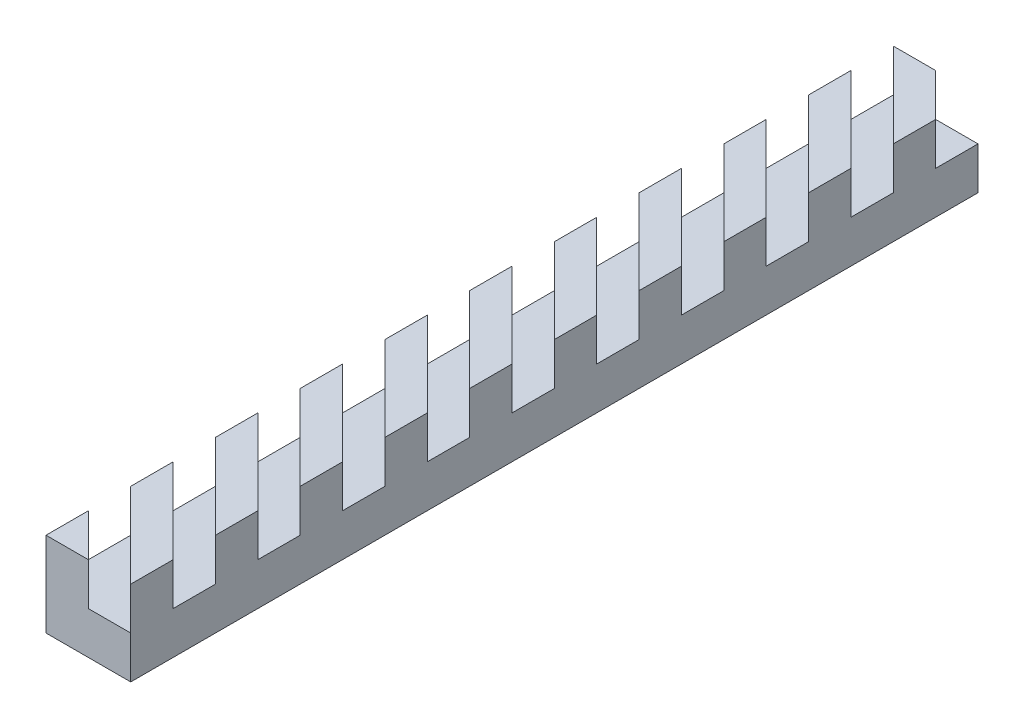
SolidWorks part; units mm, degrees
ref_plane "Front Plane" through (0, 0, 0) normal (0, 0, 1) x (1, 0, 0)
ref_plane "Top Plane" through (0, 0, 0) normal (0, 1, 0) x (1, 0, 0)
ref_plane "Right Plane" through (0, 0, 0) normal (1, 0, 0) x (0, 0, -1)
sketch "Sketch1" plane through (0, 0, 0) normal (0, 0, 1) x (1, 0, 0)
  line L1 (-53.9409, 54.9261) -> (46.0591, 54.9261)
  line L2 (-53.9409, 54.9261) -> (-53.9409, -45.0739)
  line L3 (-53.9409, -45.0739) -> (46.0591, -45.0739)
  line L4 (46.0591, 54.9261) -> (46.0591, -45.0739)
  dimension "D1" = 100
  dimension "D2" = 100
extrude "Boss-Extrude1" add sketch "Sketch1" against normal blind 1000
sketch "Sketch2" plane through (46.0591, 0, 0) normal (1, 0, 0) x (0, 0, -1)
  line L0 (1000, 54.9261) -> (0, 54.9261) construction
  line L1 (50, 54.9261) -> (100, 54.9261)
  line L2 (50, 54.9261) -> (50, 4.9261)
  line L3 (50, 4.9261) -> (100, 4.9261)
  line L4 (100, 54.9261) -> (100, 4.9261)
  point P6 (0, 0)
  dimension "D1" = 50
  dimension "D2" = 50
  dimension "D3" = 50
sketch "Sketch5" plane through (0, 54.9261, 0) normal (0, 1, 0) x (1, 0, 0)
  line L0 (46.0591, 75) -> (-53.9409, 75)
  line L1 (46.0591, 50) -> (46.0591, 100) construction
  line L2 (-53.9409, 1000) -> (-53.9409, 0) construction
  line L3 (-53.9409, 75) -> (-53.9409, 175)
  line L4 (-53.9409, 175) -> (46.0591, 75)
  dimension "D1" = 45
sketch "Sketch6" plane through (46.0591, 0, 0) normal (1, 0, 0) x (0, 0, -1)
  line L1 (50, 54.9261) -> (100, 54.9261)
  line L2 (50, 54.9261) -> (50, 4.9261)
  line L3 (50, 4.9261) -> (100, 4.9261)
  line L4 (100, 54.9261) -> (100, 4.9261)
extrude "Cut-Extrude1" cut sketch "Sketch6" along direction (0.7071, 0, 0.7071) on the side against the normal blind 1000
pattern_linear "LPattern1" count 10 spacing 100 along (0, 0, -1) count 10 spacing 100 along (0, 0, 1) of "Cut-Extrude1"
